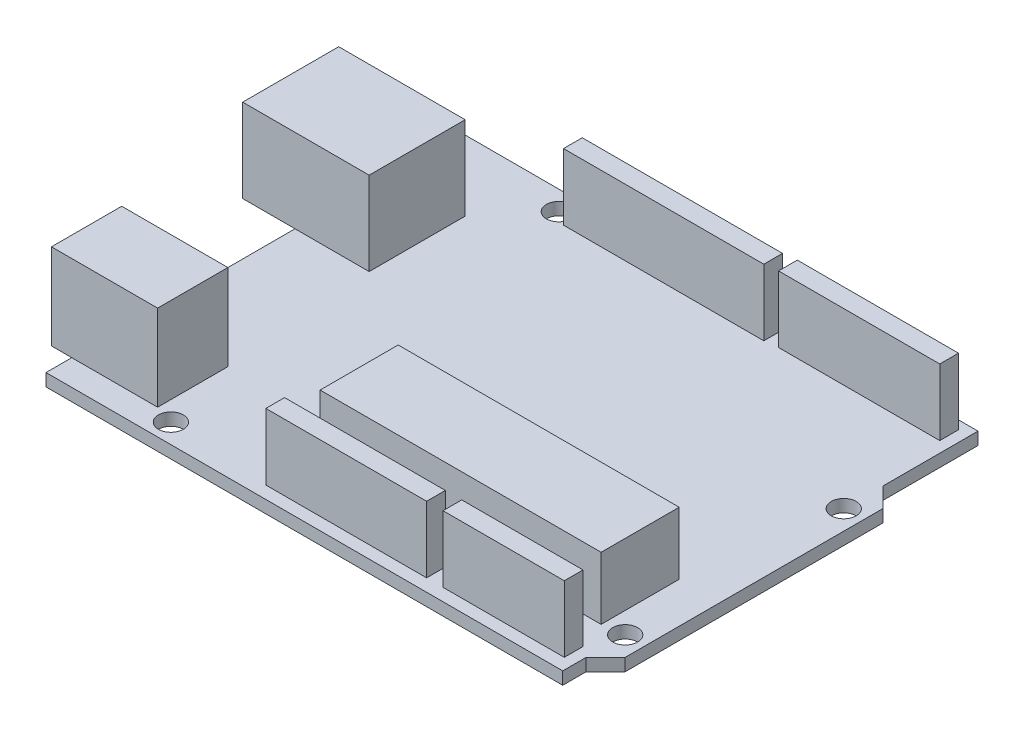
SolidWorks part; units mm, degrees
ref_plane "Front Plane" through (0, 0, 0) normal (0, 0, 1) x (1, 0, 0)
ref_plane "Top Plane" through (0, 0, 0) normal (0, 1, 0) x (1, 0, 0)
ref_plane "Right Plane" through (0, 0, 0) normal (1, 0, 0) x (0, 0, -1)
sketch "Sketch1" plane through (0, 0, 0) normal (0, 1, 0) x (1, 0, 0)
  line L0 (66.2, 41) -> (66.2, 53.2)
  line L1 (0, 0) -> (66.2, 0)
  line L2 (0, 0) -> (0, 53.2)
  line L3 (0, 53.2) -> (66.2, 53.2)
  line L4 (66.2, 0) -> (66.2, 3)
  line L8 (68.7, 38.5) -> (68.7, 5.5)
  line L9 (68.7, 38.5) -> (66.2, 41)
  line L10 (68.7, 5.5) -> (66.2, 3)
  line L12 (-6.7, 44.2) -> (9.5, 44.2)
  line L13 (-6.7, 44.2) -> (-6.7, 31.9)
  line L14 (-6.7, 31.9) -> (9.5, 31.9)
  line L15 (9.5, 44.2) -> (9.5, 31.9)
  line L16 (-2.6, 12.3) -> (11, 12.3)
  line L17 (-2.6, 12.3) -> (-2.6, 3.3)
  line L18 (-2.6, 3.3) -> (11, 3.3)
  line L19 (11, 12.3) -> (11, 3.3)
  line L20 (27.5, 17.6176) -> (63.5, 17.6176)
  line L21 (27.5, 17.6176) -> (27.5, 7.6176)
  line L22 (27.5, 7.6176) -> (63.5, 7.6176)
  line L23 (63.5, 17.6176) -> (63.5, 7.6176)
  line L24 (16.8, 51.9) -> (42.46, 51.9)
  line L25 (16.8, 51.9) -> (16.8, 49.5)
  line L26 (16.8, 49.5) -> (42.46, 49.5)
  line L27 (42.46, 51.9) -> (42.46, 49.5)
  line L28 (44.15, 52.1) -> (64.8, 52.1)
  line L29 (44.15, 52.1) -> (44.15, 49.7)
  line L30 (44.15, 49.7) -> (64.8, 49.7)
  line L31 (64.8, 52.1) -> (64.8, 49.7)
  line L32 (26.56, 4) -> (47.16, 4)
  line L33 (26.56, 4) -> (26.56, 1.6)
  line L34 (26.56, 1.6) -> (47.16, 1.6)
  line L35 (47.16, 4) -> (47.16, 1.6)
  line L36 (49.26, 4) -> (64.8, 4)
  line L37 (49.26, 4) -> (49.26, 1.6)
  line L38 (49.26, 1.6) -> (64.8, 1.6)
  line L39 (64.8, 4) -> (64.8, 1.6)
  circle A0 centre (15, 50.7) radius 1.6
  circle A1 centre (13.5, 2.5) radius 1.6
  circle A2 centre (66.2, 36) radius 1.6
  circle A3 centre (66.2, 8) radius 1.6
  dimension "D3" = 3.2
  dimension "D1" = 66.2
  dimension "D2" = 53.2
  dimension "D4" = 2.5
  dimension "D5" = 2.5
  dimension "D6" = 2.5
  dimension "D7" = 2.5
  dimension "D8" = 2.5
  dimension "D9" = 13.5
  dimension "D10" = 2.5
  dimension "D11" = 2.5
  dimension "D12" = 15
  dimension "D13" = 16.2
  dimension "D14" = 12.3
  dimension "D15" = 9.5
  dimension "D16" = 9
  dimension "D17" = 13.6
  dimension "D18" = 9
  dimension "D19" = 3.3
  dimension "D20" = 11
  dimension "D21" = 36
  dimension "D22" = 10
  dimension "D23" = 5.2
  dimension "D24" = 25.66
  dimension "D25" = 2.4
  dimension "D26" = 2.4
  dimension "D27" = 2.4
  dimension "D28" = 2.4
  dimension "D29" = 20.65
  dimension "D30" = 1.8
  dimension "D31" = 1.4
  dimension "D32" = 1.1
  dimension "D33" = 1.3
  dimension "D34" = 20.6
  dimension "D35" = 15.54
  dimension "D36" = 1.4
  dimension "D37" = 2.1
  dimension "D38" = 1.6
  dimension "D39" = 1.6
extrude "Boss-Extrude1" add sketch "Sketch1" against normal blind 1.6 contours L16 L19 L18 L2 L1 L4 L10 L8 L9 L0 L3 L12 L15 L14 A3 A2 A1 A0 L20 L23 L22 L21 L24 L27 L26 L25 L28 L31 L30 L29 L32 L35 L34 L33 L36 L39 L38 L37 | L15 L12 L2 L14 | L19 L16 L2 L18 | L23 L20 L21 L22 | L35 L32 L33 L34 | L39 L36 L37 L38 | L27 L24 L25 L26 | L31 L28 L29 L30 region at (33.982, 0, -28.2396) region at (4.75, 0, -38.05) region at (5.5, 0, -7.8) region at (45.5, 0, -12.6176) region at (29.63, 0, -50.7) region at (54.475, 0, -50.9) region at (36.86, 0, -2.8) region at (57.03, 0, -2.8)
extrude "Boss-Extrude2" add sketch "Sketch1<3>" along normal blind 10.7 contours L13 L14 L2 L12 | L15 L12 L2 L14 region at (4.75, 0, -38.05) region at (-3.35, 0, -38.05)
sketch "Sketch1<3>" plane through (0, 0, 0) normal (0, 1, 0) x (1, 0, 0) same geometry as "Sketch1"
extrude "Boss-Extrude3" add sketch "Sketch1<4>" along normal blind 11 contours L19 L16 L2 L18 | L17 L18 L2 L16 region at (5.5, 0, -7.8) region at (-1.3, 0, -7.8)
sketch "Sketch1<4>" plane through (0, 0, 0) normal (0, 1, 0) x (1, 0, 0) same geometry as "Sketch1"
extrude "Boss-Extrude4" add sketch "Sketch1<5>" along normal blind 8 contours L23 L20 L21 L22 region at (45.5, 0, -12.6176)
sketch "Sketch1<5>" plane through (0, 0, 0) normal (0, 1, 0) x (1, 0, 0) same geometry as "Sketch1"
extrude "Boss-Extrude5" add sketch "Sketch1<6>" along normal blind 8.5 contours L27 L24 L25 L26 | L31 L28 L29 L30 | L39 L36 L37 L38 | L32 L35 L34 L33 region at (29.63, 0, -50.7) region at (54.475, 0, -50.9) region at (57.03, 0, -2.8)
sketch "Sketch1<6>" plane through (0, 0, 0) normal (0, 1, 0) x (1, 0, 0) same geometry as "Sketch1"
